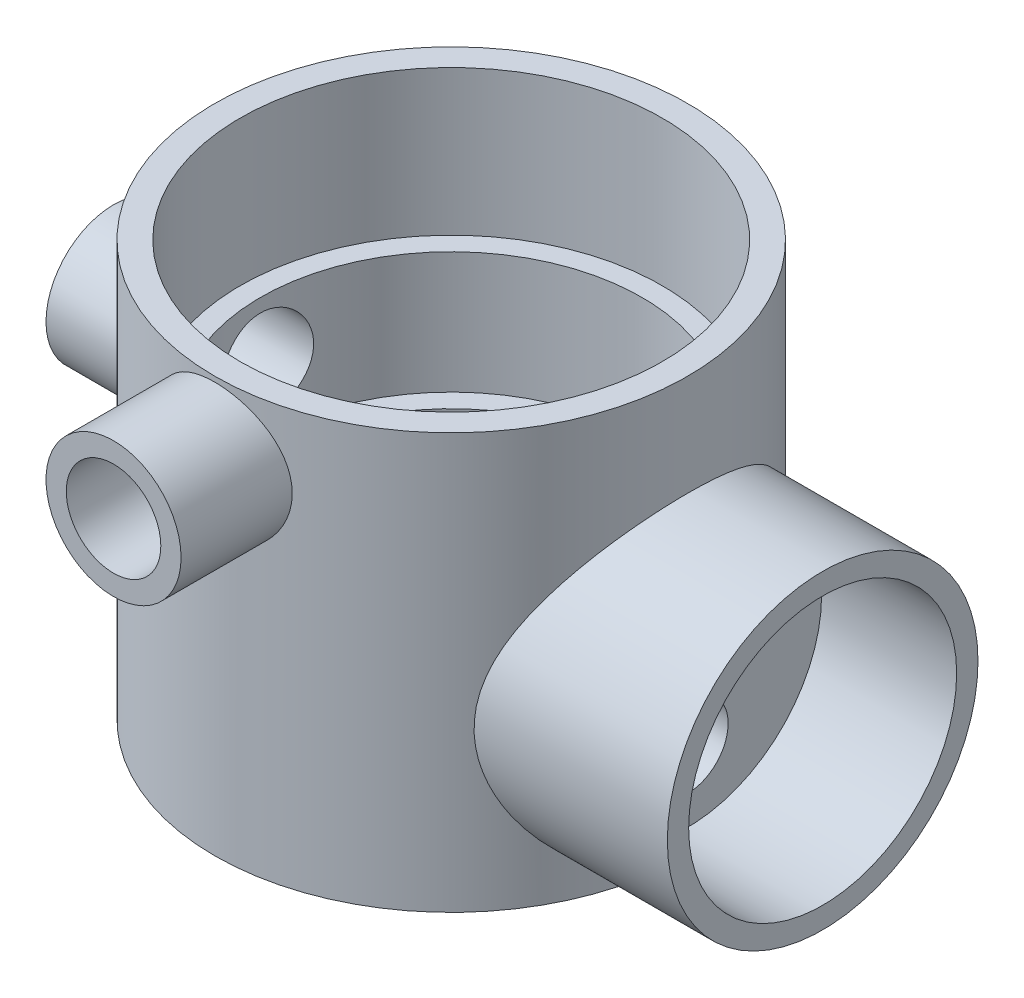
SolidWorks part; units mm, degrees
material "Acrylic (Medium-high impact)"
ref_plane "Front Plane" through (0, 0, 0) normal (0, 0, 1) x (1, 0, 0)
ref_plane "Top Plane" through (0, 0, 0) normal (0, 1, 0) x (1, 0, 0)
ref_plane "Right Plane" through (0, 0, 0) normal (1, 0, 0) x (0, 0, -1)
sketch "Sketch1" plane through (0, 0, 0) normal (0, 1, 0) x (1, 0, 0)
  circle A0 centre (0, 0) radius 35
extrude "Boss-Extrude1" add sketch "Sketch1" along normal blind 4
sketch "Sketch2" plane through (0, 4, 0) normal (0, 1, 0) x (1, 0, 0)
  circle A0 centre (0, 0) radius 7.8
extrude "Boss-Extrude2" add sketch "Sketch2" along normal blind 2
sketch "Sketch3" plane through (0, 4, 0) normal (0, 1, 0) x (1, 0, 0)
  circle A0 centre (0, 0) radius 25.25
  circle A1 centre (0, 0) radius 35
extrude "Boss-Extrude3" add sketch "Sketch3" along normal blind 18
sketch "Sketch4" plane through (0, 22, 0) normal (0, 1, 0) x (1, 0, 0)
  circle A0 centre (0, 0) radius 28.25
  circle A1 centre (0, 0) radius 35
extrude "Boss-Extrude4" add sketch "Sketch4" along normal blind 18
sketch "Sketch5" plane through (0, 40, 0) normal (0, 1, 0) x (1, 0, 0)
  circle A0 centre (0, 0) radius 31.25
  circle A1 centre (0, 0) radius 35
extrude "Boss-Extrude5" add sketch "Sketch5" along normal blind 21.5
ref_plane "Plane1" through (55, 0, 0) normal (1, 0, 0) x (0, 0, -1)
sketch "Sketch7" plane through (55, 0, 0) normal (1, 0, 0) x (0, 0, -1)
  line L1 (-35, 0) -> (35, 0) construction
  circle A1 centre (0, 23.5) radius 23
  dimension "D1" = 46
  dimension "D2" = 23.5
extrude "Boss-Extrude7" add sketch "Sketch7" against normal up to next contours A1 region at (55, 23.5, 0)
sketch "Sketch10" plane through (55, 0, 0) normal (1, 0, 0) x (0, 0, -1)
  circle A0 centre (0, 23.5) radius 19.8438
  dimension "D1" = 39.6875
extrude "Cut-Extrude1" cut sketch "Sketch10" against normal blind 20
sketch "Sketch11" plane through (35, 0, 0) normal (1, 0, 0) x (0, 0, -1)
  line L0 (-35, 0) -> (35, 0) construction
  circle A0 centre (0, 14) radius 6
  dimension "D1" = 14
extrude "Cut-Extrude2" cut sketch "Sketch11" against normal up to next
ref_plane "Plane4" through (-50, 0, 0) normal (1, 0, 0) x (0, 0, -1)
sketch "Sketch12" plane through (-50, 0, 0) normal (1, 0, 0) x (0, 0, -1)
  circle A1 centre (0, 31) radius 10
  dimension "D1" = 20
extrude "Boss-Extrude8" add sketch "Sketch12" along normal up to next
sketch "Sketch13" plane through (-50, 0, 0) normal (-1, 0, 0) x (0, 0, 1)
  circle A0 centre (0, 31) radius 7
extrude "Cut-Extrude3" cut sketch "Sketch13" against normal up to next
ref_plane "Plane5" through (0, 0, 50) normal (0, 0, 1) x (1, 0, 0)
sketch "Sketch14" plane through (0, 0, 50) normal (0, 0, 1) x (1, 0, 0)
  line L0 (35, 61.5) -> (-35, 61.5) construction
  circle A0 centre (0, 50.75) radius 10
  dimension "D1" = 10.75
  dimension "D2" = 20
extrude "Boss-Extrude9" add sketch "Sketch14" against normal up to surface (16.459 mm away) contours A0 region at (0, 50.75, 50) up to face at (0, 61.5, 35)
sketch "Sketch15" plane through (0, 0, 50) normal (0, 0, 1) x (1, 0, 0)
  circle A0 centre (0, 50.75) radius 7
extrude "Cut-Extrude4" cut sketch "Sketch15" against normal up to next
